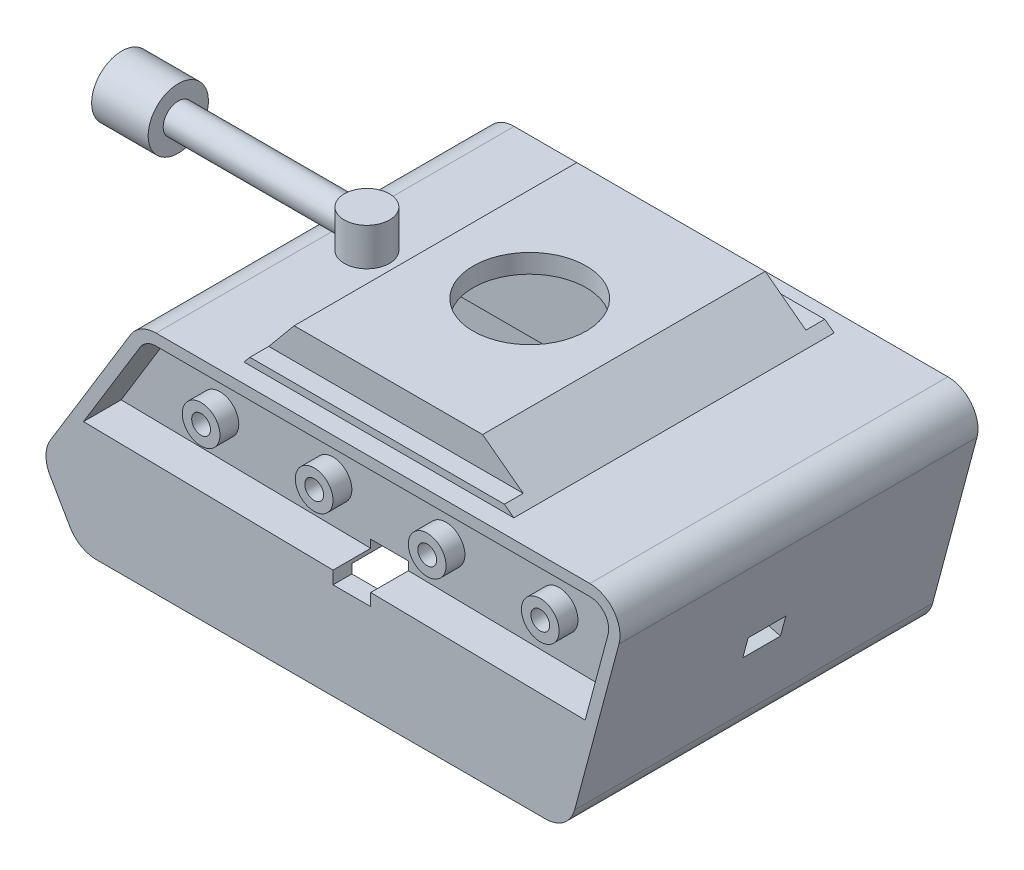
SolidWorks part; units mm, degrees
note: The reader was unsure of these and kept them because the rebuilt part matched: shared geometry of "Croquis5<3>".
ref_plane "Alzado" through (0, 0, 0) normal (0, 0, 1) x (1, 0, 0)
ref_plane "Planta" through (0, 0, 0) normal (0, 1, 0) x (1, 0, 0)
ref_plane "Vista lateral" through (0, 0, 0) normal (1, 0, 0) x (0, 0, -1)
sketch "Croquis1" plane through (0, 0, 0) normal (0, 0, 1) x (1, 0, 0)
  line L0 (-39.1037, 52.6381) -> (75.9856, 52.6381)
  line L1 (83.714, 42.5712) -> (71.946, -1.4288)
  line L2 (-45.9325, 48.8057) -> (-67.1665, 14.0129)
  line L3 (-67.266, 5.8453) -> (-61.9502, -3.3619)
  line L4 (-55.022, -7.3619) -> (64.2176, -7.3619)
  line L5 (-20.7848, 52.6381) -> (-12.4781, 62.6381)
  line L6 (-12.4781, 62.6381) -> (37.5219, 62.6381)
  line L7 (37.5219, 62.6381) -> (50.8196, 52.6381)
  arc A0 (71.946, -1.4288) -> (64.2176, -7.3619) centre (64.2176, 0.6381) cw
  arc A1 (-61.9502, -3.3619) -> (-55.022, -7.3619) centre (-55.022, 0.6381) ccw
  arc A2 (-67.1665, 14.0129) -> (-67.266, 5.8453) centre (-60.3378, 9.8453) ccw
  arc A3 (-39.1037, 52.6381) -> (-45.9325, 48.8057) centre (-39.1037, 44.6381) ccw
  arc A4 (75.9856, 52.6381) -> (83.714, 42.5712) centre (75.9856, 44.6381) cw
  point P9 (70.3592, -7.3619)
  point P12 (-59.6408, -7.3619)
  point P15 (-69.6408, 9.9586)
  point P18 (-43.5935, 52.6381)
  point P21 (86.4065, 52.6381)
  dimension "D7" = 8
  dimension "D1" = 140
  dimension "D2" = 50
  dimension "D3" = 20
  dimension "D4" = 130
  dimension "D5" = 130
  dimension "D6" = 60
  dimension "D8" = 10
  dimension "D9" = 50
  dimension "D10" = 13
  dimension "D11" = 16.6382
extrude "Saliente-Extruir2" add sketch "Croquis1" against normal blind 75 contours A4 L0 A3 L2 A2 L3 A1 L4 A0 L1 | L7 L6 L5 L0
ref_plane "Plano1" through (0, 0, -37.5) normal (0, 0, 1) x (1, 0, 0)
sketch "Croquis2" plane through (0, 0, -37.5) normal (0, 0, 1) x (1, 0, 0)
  line L18 (75.9856, 47.6381) -> (49.1493, 47.6381)
  line L19 (49.1493, 47.6381) -> (35.8516, 57.6381)
  line L20 (35.8516, 57.6381) -> (-10.1314, 57.6381)
  line L21 (-10.1314, 57.6381) -> (-18.4381, 47.6381)
  line L22 (-18.4381, 47.6381) -> (-39.1037, 47.6381)
  line L23 (-41.6645, 46.201) -> (-62.8986, 11.4082)
  line L24 (-62.9359, 8.3453) -> (-57.6201, -0.8619)
  line L25 (-55.022, -2.3619) -> (64.2176, -2.3619)
  line L26 (67.1158, -0.137) -> (78.8838, 43.863)
  line L27 (75.9856, 47.6381) -> (49.1493, 47.6381)
  line L28 (49.1493, 47.6381) -> (35.8516, 57.6381)
  line L29 (35.8516, 57.6381) -> (-10.1314, 57.6381)
  line L30 (-10.1314, 57.6381) -> (-18.4381, 47.6381)
  line L31 (-18.4381, 47.6381) -> (-39.1037, 47.6381)
  line L32 (-41.6645, 46.201) -> (-62.8986, 11.4082)
  line L33 (-62.9359, 8.3453) -> (-57.6201, -0.8619)
  line L34 (-55.022, -2.3619) -> (64.2176, -2.3619)
  line L35 (67.1158, -0.137) -> (78.8838, 43.863)
  arc A10 (78.8838, 43.863) -> (75.9856, 47.6381) centre (75.9856, 44.6381) ccw
  arc A11 (-39.1037, 47.6381) -> (-41.6645, 46.201) centre (-39.1037, 44.6381) ccw
  arc A12 (-62.8986, 11.4082) -> (-62.9359, 8.3453) centre (-60.3378, 9.8453) ccw
  arc A13 (-57.6201, -0.8619) -> (-55.022, -2.3619) centre (-55.022, 0.6381) ccw
  arc A14 (64.2176, -2.3619) -> (67.1158, -0.137) centre (64.2176, 0.6381) ccw
  arc A15 (78.8838, 43.863) -> (75.9856, 47.6381) centre (75.9856, 44.6381) ccw
  arc A16 (-39.1037, 47.6381) -> (-41.6645, 46.201) centre (-39.1037, 44.6381) ccw
  arc A17 (-62.8986, 11.4082) -> (-62.9359, 8.3453) centre (-60.3378, 9.8453) ccw
  arc A18 (-57.6201, -0.8619) -> (-55.022, -2.3619) centre (-55.022, 0.6381) ccw
  arc A19 (64.2176, -2.3619) -> (67.1158, -0.137) centre (64.2176, 0.6381) ccw
  dimension "D1" = 5
extrude "Cortar-Extruir1" cut sketch "Croquis2" against normal mid plane 65
sketch "Croquis3" plane through (0, -7.3619, 0) normal (0, -1, 0) x (1, 0, 0)
  line L0 (-50.022, -5) -> (-50.022, -70)
  line L1 (-50.022, -70) -> (59.978, -70)
  line L2 (59.978, -70) -> (59.978, -5)
  line L3 (59.978, -5) -> (-50.022, -5)
  line L4 (-55.022, -75) -> (-55.022, 0) construction
  line L6 (-55.022, 0) -> (64.2176, 0) construction
  point P2 (4.978, -5)
  dimension "D1" = 110
  dimension "D2" = 65
  dimension "D3" = 60
  dimension "D4" = 5
extrude "Cortar-Extruir2" cut sketch "Croquis3" against normal blind 55 draft 7
sketch "Croquis4" plane through (0, 62.6381, 0) normal (0, 1, 0) x (1, 0, 0)
  line L0 (-12.4781, 75) -> (37.5219, 75) construction
  line L1 (37.5219, 75) -> (37.5219, 0) construction
  circle A0 centre (12.5219, 37.5) radius 15
  dimension "D1" = 30
  dimension "D2" = 37.5
  dimension "D3" = 25
extrude "Cortar-Extruir3" cut sketch "Croquis4" against normal blind 55
sketch "Croquis5" plane through (0, 0, 0) normal (0, 0, 1) x (1, 0, 0)
  line L0 (-20.7848, 52.6381) -> (50.8196, 52.6381)
  line L1 (83.714, 42.5712) -> (71.946, -1.4288) construction
  line L2 (-19.2215, 54.5201) -> (48.317, 54.5201)
  line L3 (-20.7848, 52.6381) -> (-12.4781, 62.6381) construction
  line L4 (37.5219, 62.6381) -> (50.8196, 52.6381) construction
  line L5 (-19.2215, 54.5201) -> (-20.7848, 52.6381)
  line L6 (48.317, 54.5201) -> (50.8196, 52.6381)
  circle A0 centre (57.83, 32.6381) radius 5
  circle A1 centre (27.83, 32.6381) radius 5
  circle A2 centre (-2.17, 32.6381) radius 5
  circle A3 centre (-32.17, 32.6381) radius 5
  circle A4 centre (-32.17, 32.6381) radius 2.5
  circle A5 centre (-2.17, 32.6381) radius 2.5
  circle A6 centre (27.83, 32.6381) radius 2.5
  circle A7 centre (57.83, 32.6381) radius 2.5
  point P12 (15.0174, 52.6381)
  point P16 (77.83, 20.5712)
  dimension "D1" = 10
  dimension "D5" = 20
  dimension "D7" = 5
  dimension "D8" = 5
  dimension "D9" = 5
  dimension "D10" = 5
  dimension "D2" = 30
  dimension "D3" = 30
  dimension "D4" = 30
  dimension "D6" = 20
extrude "Saliente-Extruir3" add sketch "Croquis5" along normal blind 5 contours A3 | A2 | A1 | A0 A7
extrude "Saliente-Extruir4" add sketch "Croquis5<3>" along normal blind 5
sketch "Croquis5<3>" plane through (0, 0, 0) normal (0, 0, 1) x (1, 0, 0) same geometry as "Croquis5"
sketch "Croquis6" plane through (0, 0, -75) normal (0, 0, -1) x (-1, 0, 0)
  line L0 (-50.8196, 52.6381) -> (20.7848, 52.6381)
  line L1 (20.7848, 52.6381) -> (19.2215, 54.5201)
  line L2 (19.2215, 54.5201) -> (-48.317, 54.5201)
  line L3 (-48.317, 54.5201) -> (-50.8196, 52.6381)
  line L4 (-83.714, 42.5712) -> (-71.946, -1.4288) construction
  line L5 (-50.8196, 52.6381) -> (-75.9856, 52.6381) construction
  circle A0 centre (-57.83, 32.6381) radius 5
  circle A1 centre (-27.83, 32.6381) radius 5
  circle A2 centre (2.17, 32.6381) radius 5
  circle A3 centre (32.17, 32.6381) radius 5
  circle A4 centre (-57.83, 32.6381) radius 2.5004
  circle A5 centre (-27.83, 32.6381) radius 2.5
  circle A6 centre (2.17, 32.6381) radius 2.5
  circle A7 centre (32.17, 32.6381) radius 2.5
  point P18 (-77.83, 20.5712)
  dimension "D1" = 10
  dimension "D7" = 5.0008
  dimension "D8" = 5
  dimension "D9" = 5
  dimension "D10" = 5
  dimension "D2" = 30
  dimension "D3" = 30
  dimension "D4" = 30
  dimension "D5" = 20
  dimension "D6" = 20
extrude "Saliente-Extruir5" add sketch "Croquis6" along normal blind 5
sketch "Croquis7" plane through (0, 0, -75) normal (0, 0, -1) x (-1, 0, 0)
  line L0 (-64.2176, -7.3619) -> (55.022, -7.3619)
  line L1 (-71.946, -1.4288) -> (-83.714, 42.5712)
  line L2 (-80.8159, 43.3463) -> (-75.7505, 24.407)
  line L3 (61.9502, -3.3619) -> (67.266, 5.8453)
  line L4 (-75.7505, 24.407) -> (57.3084, 24.407)
  line L7 (45.9325, 48.8057) -> (67.1665, 14.0129)
  line L8 (-75.9856, 52.6381) -> (39.1037, 52.6381)
  line L11 (-75.9856, 49.6381) -> (39.1037, 49.6381)
  line L12 (43.3717, 47.2429) -> (57.3084, 24.407)
  line L15 (43.3717, 47.2429) -> (58.2622, 22.8442) construction
  line L16 (-78.8559, 24.407) -> (-83.714, 42.5712) construction
  line L17 (-75.9578, 25.1821) -> (-80.8159, 43.3463) construction
  line L18 (45.9325, 48.8057) -> (60.823, 24.407) construction
  arc A0 (-64.2176, -7.3619) -> (-71.946, -1.4288) centre (-64.2176, 0.6381) cw
  arc A1 (55.022, -7.3619) -> (61.9502, -3.3619) centre (55.022, 0.6381) ccw
  arc A2 (67.266, 5.8453) -> (67.1665, 14.0129) centre (60.3378, 9.8453) ccw
  arc A3 (-83.714, 42.5712) -> (-75.9856, 52.6381) centre (-75.9856, 44.6381) cw
  arc A4 (39.1037, 52.6381) -> (45.9325, 48.8057) centre (39.1037, 44.6381) cw
  arc A5 (-80.8159, 43.3463) -> (-75.9856, 49.6381) centre (-75.9856, 44.6381) cw
  arc A6 (39.1037, 49.6381) -> (43.3717, 47.2429) centre (39.1037, 44.6381) cw
  dimension "D2" = 3
extrude "Saliente-Extruir6" add sketch "Croquis7" along normal blind 10
sketch "Croquis8" plane through (0, 0, 0) normal (0, 0, 1) x (1, 0, 0)
  line L0 (-67.266, 5.8453) -> (-61.9502, -3.3619)
  line L1 (-55.022, -7.3619) -> (64.2176, -7.3619)
  line L4 (-39.1037, 52.6381) -> (75.9856, 52.6381)
  line L5 (-67.1665, 14.0129) -> (-61.858, 22.7111)
  line L6 (83.714, 42.5712) -> (77.83, 20.5712)
  line L7 (71.946, -1.4288) -> (77.83, 20.5712)
  line L8 (83.714, 42.5712) -> (71.946, -1.4288) construction
  line L9 (74.7372, 20.6185) -> (-58.376, 22.6578)
  line L10 (-61.858, 22.7111) -> (-45.9325, 48.8057)
  line L12 (-58.376, 22.6578) -> (-43.3717, 47.2429)
  line L13 (-39.1037, 49.6381) -> (75.9856, 49.6381)
  line L14 (74.9319, 21.3463) -> (80.8159, 43.3463)
  line L15 (-59.2972, 21.1483) -> (-43.3717, 47.2429) construction
  line L16 (77.83, 20.5712) -> (83.714, 42.5712) construction
  line L17 (74.9319, 21.3463) -> (74.7372, 20.6185)
  arc A0 (-39.1037, 52.6381) -> (-45.9325, 48.8057) centre (-39.1037, 44.6381) ccw
  arc A1 (-67.1665, 14.0129) -> (-67.266, 5.8453) centre (-60.3378, 9.8453) ccw
  arc A2 (-61.9502, -3.3619) -> (-55.022, -7.3619) centre (-55.022, 0.6381) ccw
  arc A3 (75.9856, 52.6381) -> (83.714, 42.5712) centre (75.9856, 44.6381) cw
  arc A4 (64.2176, -7.3619) -> (71.946, -1.4288) centre (64.2176, 0.6381) ccw
  arc A5 (-39.1037, 49.6381) -> (-43.3717, 47.2429) centre (-39.1037, 44.6381) ccw
  arc A6 (75.9856, 49.6381) -> (80.8159, 43.3463) centre (75.9856, 44.6381) cw
  dimension "D1" = 3
extrude "Saliente-Extruir7" add sketch "Croquis8" along normal blind 10
sketch "Croquis9" plane through (0, 52.6381, 0) normal (0, 1, 0) x (1, 0, 0)
  circle A0 centre (-30.1457, 36.9667) radius 6
  dimension "D1" = 12
extrude "Saliente-Extruir8" add sketch "Croquis9" along normal blind 10
ref_plane "Plano2" through (-30, 0, 0) normal (1, 0, 0) x (0, 0, -1)
sketch "Croquis10" plane through (-30, 0, 0) normal (1, 0, 0) x (0, 0, -1)
  line L0 (42.9667, 62.6381) -> (30.9667, 62.6381) construction
  circle A0 centre (36.7741, 58.1381) radius 4
  dimension "D1" = 8
  dimension "D2" = 4.5
extrude "Saliente-Extruir9" add sketch "Croquis10" against normal blind 50
sketch "Croquis11" plane through (-80, 0, 0) normal (-1, 0, 0) x (0, 0, 1)
  circle A0 centre (-36.7741, 58.1381) radius 8
  circle A1 centre (-36.7741, 58.1381) radius 4
  dimension "D1" = 16
extrude "Saliente-Extruir10" add sketch "Croquis11" along normal blind 15 separate body
sketch "Croquis13" plane through (0, 0, -85) normal (0, 0, -1) x (-1, 0, 0)
  line L1 (-17.83, 23.7481) -> (-7.83, 23.7481)
  line L2 (-17.83, 23.7481) -> (-17.83, 18.2481)
  line L3 (-17.83, 18.2481) -> (-7.83, 18.2481)
  line L4 (-7.83, 23.7481) -> (-7.83, 18.2481)
  line L5 (-17.83, 23.7481) -> (-7.83, 18.2481) construction
  line L6 (-17.83, 18.2481) -> (-7.83, 23.7481) construction
  line L7 (-83.714, 42.5712) -> (-71.946, -1.4288) construction
  line L9 (-64.2176, -7.3619) -> (55.022, -7.3619) construction
  point P0 (-12.83, 20.9981)
  point P9 (-77.83, 20.5712)
  dimension "D1" = 10
  dimension "D2" = 5.5
  dimension "D3" = 31.11
  dimension "D4" = 60
extrude "Cortar-Extruir4" cut sketch "Croquis13" against normal through all
sketch "Croquis14" plane through (67.4998, -18.0531, 0) normal (0.966, -0.2584, 0) x (0, 0, -1)
  line L1 (30, 40.5802) -> (40, 40.5802)
  line L2 (30, 40.5802) -> (30, 35.0802)
  line L3 (30, 35.0802) -> (40, 35.0802)
  line L4 (40, 40.5802) -> (40, 35.0802)
  line L5 (30, 40.5802) -> (40, 35.0802) construction
  line L6 (30, 35.0802) -> (40, 40.5802) construction
  line L7 (-10, 17.2086) -> (-10, 62.7551) construction
  line L8 (85, 9.4802) -> (-10, 9.4802) construction
  point P0 (35, 37.8302)
  dimension "D1" = 10
  dimension "D2" = 5.5
  dimension "D3" = 31.1
  dimension "D4" = 40
extrude "Cortar-Extruir5" cut sketch "Croquis14" against normal blind 10
sketch "Croquis15" plane through (-55.1697, 33.6701, 0) normal (-0.8536, 0.5209, 0) x (0, 0, 1)
  line L0 (-85, 17.7317) -> (10, 17.7317) construction
  line L1 (-45, -12.2683) -> (-35, -12.2683)
  line L2 (-45, -12.2683) -> (-45, -17.7683)
  line L3 (-45, -17.7683) -> (-35, -17.7683)
  line L4 (-35, -12.2683) -> (-35, -17.7683)
  line L5 (-45, -12.2683) -> (-35, -17.7683) construction
  line L6 (-45, -17.7683) -> (-35, -12.2683) construction
  line L7 (-85, -23.0288) -> (-85, 17.7317) construction
  point P0 (-40, -15.0183)
  dimension "D1" = 10
  dimension "D2" = 5.5
  dimension "D3" = 30
  dimension "D4" = 40
extrude "Cortar-Extruir6" cut sketch "Croquis15" against normal blind 10
sketch "Croquis16" plane through (0, 0, -5) normal (0, 0, -1) x (-1, 0, 0)
  line L0 (58.9209, 21.7649) -> (-74.4526, 19.5544)
  line L10 (59.3521, -1.8619) -> (64.6679, 7.3453)
  line L11 (-64.2176, -4.3619) -> (55.022, -4.3619)
  line L12 (-80.8159, 43.3463) -> (-69.0479, -0.6537)
  line L13 (39.1037, 49.6381) -> (-75.9856, 49.6381)
  line L14 (64.6057, 12.4501) -> (43.3717, 47.2429)
  line L15 (59.3521, -1.8619) -> (64.6679, 7.3453)
  line L16 (-64.2176, -4.3619) -> (55.022, -4.3619)
  line L17 (-74.4526, 19.5544) -> (-69.0479, -0.6537)
  line L19 (64.6057, 12.4501) -> (58.9209, 21.7649)
  arc A10 (64.6679, 7.3453) -> (64.6057, 12.4501) centre (60.3378, 9.8453) ccw
  arc A11 (55.022, -4.3619) -> (59.3521, -1.8619) centre (55.022, 0.6381) ccw
  arc A12 (-69.0479, -0.6537) -> (-64.2176, -4.3619) centre (-64.2176, 0.6381) ccw
  arc A13 (-75.9856, 49.6381) -> (-80.8159, 43.3463) centre (-75.9856, 44.6381) ccw
  arc A14 (43.3717, 47.2429) -> (39.1037, 49.6381) centre (39.1037, 44.6381) ccw
  arc A15 (64.6679, 7.3453) -> (64.6057, 12.4501) centre (60.3378, 9.8453) ccw
  arc A16 (55.022, -4.3619) -> (59.3521, -1.8619) centre (55.022, 0.6381) ccw
  arc A17 (-69.0479, -0.6537) -> (-64.2176, -4.3619) centre (-64.2176, 0.6381) ccw
  arc A19 (43.3717, 47.2429) -> (39.1037, 49.6381) centre (39.1037, 44.6381) ccw
  dimension "D1" = 3
extrude "Cortar-Extruir8" cut sketch "Croquis16" against normal blind 10
sketch "Croquis18" plane through (0, 0, -70) normal (0, 0, 1) x (1, 0, 0)
  line L0 (-64.6057, 12.4501) -> (-59.1393, 21.407)
  line L2 (-64.6679, 7.3453) -> (-59.3521, -1.8619)
  line L3 (-55.022, -4.3619) -> (64.2176, -4.3619)
  line L22 (69.0479, -0.6537) -> (74.9481, 21.407)
  line L23 (-57.3084, 21.407) -> (74.9481, 21.407)
  line L24 (-57.3084, 21.407) -> (-59.1393, 21.407)
  arc A0 (-64.6057, 12.4501) -> (-64.6679, 7.3453) centre (-60.3378, 9.8453) ccw
  arc A1 (-59.3521, -1.8619) -> (-55.022, -4.3619) centre (-55.022, 0.6381) ccw
  arc A16 (64.2176, -4.3619) -> (69.0479, -0.6537) centre (64.2176, 0.6381) ccw
extrude "Cortar-Extruir9" cut sketch "Croquis18" against normal blind 10
